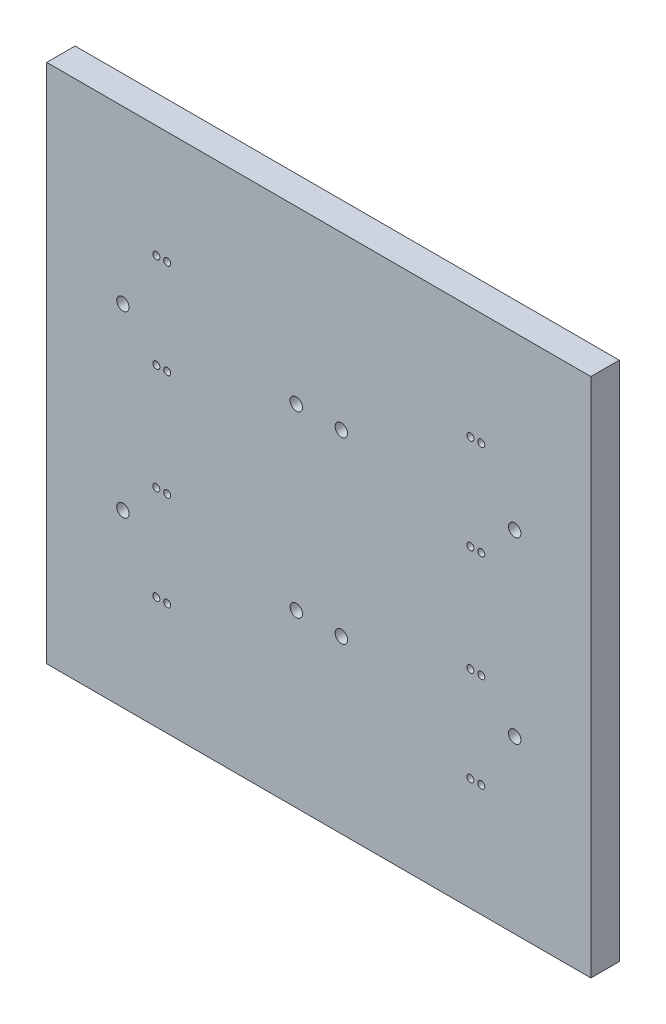
SolidWorks part; units mm, degrees
ref_plane "Front Plane" through (0, 0, 0) normal (0, 0, 1) x (1, 0, 0)
ref_plane "Top Plane" through (0, 0, 0) normal (0, 1, 0) x (1, 0, 0)
ref_plane "Right Plane" through (0, 0, 0) normal (1, 0, 0) x (0, 0, -1)
sketch "Sketch1" plane through (0, 0, 0) normal (0, 0, 1) x (1, 0, 0)
  line L1 (0, 0) -> (350, 0)
  line L2 (0, 0) -> (0, -335)
  line L3 (0, -335) -> (350, -335)
  line L4 (350, 0) -> (350, -335)
  circle A0 centre (70.5, -262.64) radius 2.25
  circle A1 centre (77.5, -262.64) radius 2.25
  circle A2 centre (77.5, -201.64) radius 2.25
  circle A3 centre (70.5, -201.64) radius 2.25
  circle A8 centre (49, -225) radius 4
  circle A9 centre (160.5, -225) radius 4
  dimension "D3" = 4.5
  dimension "D4" = 4.5
  dimension "D8" = 4.5
  dimension "D9" = 4.5
  dimension "D11" = 49
  dimension "D12" = 160.5
  dimension "D13" = 8
  dimension "D21" = 8
  dimension "D1" = 335
  dimension "D2" = 350
  dimension "D5" = 72.36
  dimension "D6" = 70.5
  dimension "D7" = 7
  dimension "D10" = 133.36
  dimension "D20" = 110
extrude "Boss-Extrude1" add sketch "Sketch1" along normal blind 18.25
ref_plane "Plane2" through (0, -167.5, 0) normal (0, 1, 0) x (1, 0, 0)
ref_plane "Plane3" through (175, 0, 0) normal (1, 0, 0) x (0, 0, -1)
mirror "Mirror2" about plane through (175, 0, 0) normal (1, 0, 0) of face at (164.5, -225, 18.25) of face at (53, -225, 18.25) of face at (72.75, -262.64, 18.25) of face at (79.75, -262.64, 18.25) of face at (79.75, -201.64, 18.25) of face at (72.75, -201.64, 18.25)
mirror "Mirror3" about plane through (0, -167.5, 0) normal (0, 1, 0) of face at (164.5, -225, 18.25) of face at (185.5, -225, 18.25) of face at (297, -225, 18.25) of face at (53, -225, 18.25) of face at (277.25, -262.64, 18.25) of face at (270.25, -262.64, 18.25) of face at (277.25, -201.64, 18.25) of face at (270.25, -201.64, 18.25) of face at (79.75, -262.64, 18.25) of face at (72.75, -262.64, 18.25) of face at (79.75, -201.64, 18.25) of face at (72.75, -201.64, 18.25)
